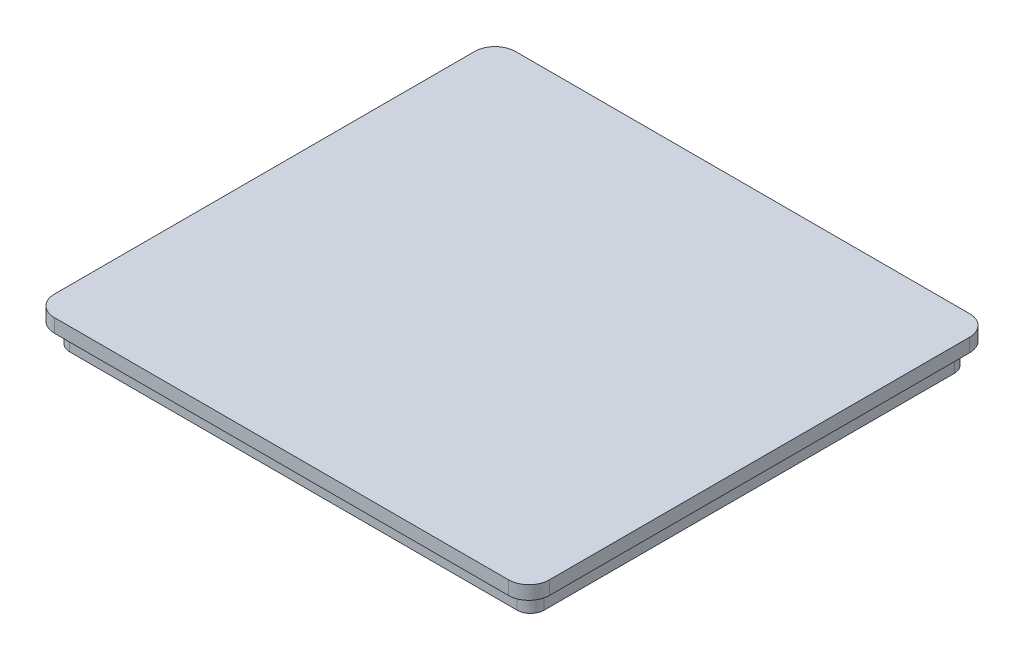
SolidWorks part; units mm, degrees
ref_plane "Alzado" through (0, 0, 0) normal (0, 0, 1) x (1, 0, 0)
ref_plane "Planta" through (0, 0, 0) normal (0, 1, 0) x (1, 0, 0)
ref_plane "Vista lateral" through (0, 0, 0) normal (1, 0, 0) x (0, 0, -1)
sketch "Croquis1" plane through (0, 0, 0) normal (0, 1, 0) x (1, 0, 0)
  line L1 (35, -51.2683) -> (-35, -51.2683)
  line L2 (35, -51.2683) -> (35, 13.2317)
  line L3 (35, 13.2317) -> (-35, 13.2317)
  line L4 (-35, -51.2683) -> (-35, 13.2317)
  line L5 (35, -51.2683) -> (-35, 13.2317) construction
  line L6 (35, 13.2317) -> (-35, -51.2683) construction
  point P0 (0, -19.0183)
  dimension "D1" = 70
  dimension "D2" = 64.5
extrude "Saliente-Extruir1" add sketch "Croquis1" along normal blind 3
fillet "Redondeo1" radius 2 4 edges at (-35, 1.5, -13.2317) (35, 1.5, -13.2317) (35, 1.5, 51.2683) (-35, 1.5, 51.2683)
shell "Vaciado2" thickness 2 removed face at (0, 0, 19.0183) removed face at (0, 3, 19.0183)
sketch "Croquis4" plane through (0, 3, 0) normal (0, 1, 0) x (1, 0, 0)
  line L0 (0, 11.2317) -> (0, -49.2683) construction
  line L1 (33, 11.2317) -> (-33, 11.2317) construction
  line L2 (-33, -49.2683) -> (33, -49.2683) construction
  line L3 (-33, -19.0183) -> (33, -19.0183) construction
  line L4 (-33, 11.2317) -> (-33, -49.2683) construction
  line L5 (33, -49.2683) -> (33, 11.2317) construction
  line L7 (33.5, -53.0183) -> (-33.5, -53.0183)
  line L8 (36.5, -50.0183) -> (36.5, 11.9817)
  line L9 (33.5, 14.9817) -> (-33.5, 14.9817)
  line L10 (-36.5, -50.0183) -> (-36.5, 11.9817)
  line L11 (36.5, -53.0183) -> (-36.5, 14.9817) construction
  line L12 (36.5, 14.9817) -> (-36.5, -53.0183) construction
  arc A0 (36.5, 11.9817) -> (33.5, 14.9817) centre (33.5, 11.9817) ccw
  arc A1 (33.5, -53.0183) -> (36.5, -50.0183) centre (33.5, -50.0183) ccw
  arc A2 (-33.5, -53.0183) -> (-36.5, -50.0183) centre (-33.5, -50.0183) cw
  arc A3 (-33.5, 14.9817) -> (-36.5, 11.9817) centre (-33.5, 11.9817) ccw
  point P12 (0, -19.0183)
  dimension "D3" = 3
  dimension "D1" = 68
  dimension "D2" = 73
extrude "Saliente-Extruir2" add sketch "Croquis4" along normal blind 2
